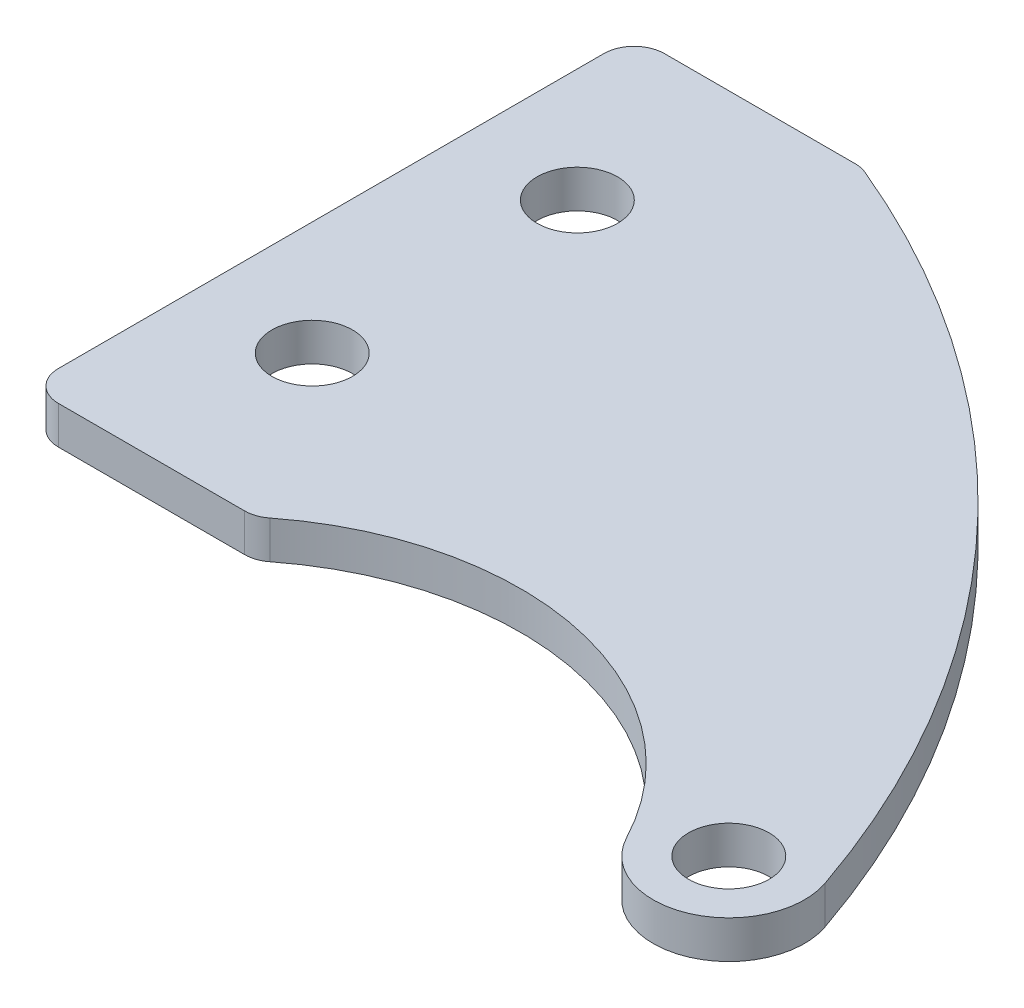
SolidWorks part; units mm, degrees
material "6061-T6 (SS)"
ref_plane "Front" through (0, 0, 0) normal (0, 0, 1) x (1, 0, 0)
ref_plane "Top" through (0, 0, 0) normal (0, 1, 0) x (1, 0, 0)
ref_plane "Right" through (0, 0, 0) normal (1, 0, 0) x (0, 0, -1)
sketch "Sketch1" plane through (0, 0, 0) normal (0, 1, 0) x (1, 0, 0)
  line L1 (0, 50.8) -> (19.05, 50.8)
  line L4 (0, 50.8) -> (0, 0)
  line L6 (0, 0) -> (19.05, 0)
  arc A0 (69.5081, -2.7071) -> (57.8724, -7.704) centre (63.5, -4.7625) cw
  arc A3 (19.05, 0) -> (57.8724, -7.704) centre (35.3619, -19.47) cw
  arc A6 (69.5081, -2.7071) -> (19.05, 50.8) centre (-14.6058, -31.483) ccw
  point P7 (69.251, -2.0703)
  dimension "D1" = 19.05
  dimension "D2" = 4.7625
  dimension "D3" = 6.35
  dimension "D4" = 63.5
  dimension "D6" = 88.9
  dimension "D7" = 25.4
  dimension "D5" = 50.8
extrude "Boss-Extrude1" add sketch "Sketch1" along normal blind 3.175
hole_wizard "1/4 Clearance Hole2" positions "Sketch4" profile "Sketch3" hole size "1/4" standard "ANSI Inch" end condition through all
sketch "Sketch4" plane through (0, 0, 0) normal (0, -1, 0) x (-1, 0, 0)
  point P0 (-63.5, -4.7625)
sketch "Sketch3" plane through (63.5, 0, 4.7625) normal (1, 0, 0) x (0, 0, -1)
  line L0 (0, 0) -> (0, 3.175)
  line L1 (0, 3.175) -> (3.3782, 3.175)
  line L2 (3.3782, 3.175) -> (3.3782, 0)
  line L5 (3.3782, 0) -> (0, 0)
  line L11 (0, -6.35) -> (0, 107.95) construction
  dimension "Thru Hole Dia." = 6.7564
  dimension "Thru Hole Depth" = 3.175
hole_wizard "1/4 Clearance Hole1" positions "Sketch7" profile "Sketch8" hole size "1/4" standard "ANSI Inch" end condition through all
sketch "Sketch7" plane through (0, 3.175, 0) normal (0, 1, 0) x (1, 0, 0)
  line L9 (9.525, 0) -> (9.525, 14.2875) construction
  line L10 (0, 0) -> (19.05, 0) construction
  line L11 (9.525, 14.2875) -> (9.525, 36.5125) construction
  line L12 (9.525, 36.5125) -> (9.525, 50.8) construction
  line L13 (19.05, 50.8) -> (0, 50.8) construction
  point P0 (9.525, 36.5125)
  point P2 (9.525, 14.2875)
  dimension "D1" = 22.225
sketch "Sketch8" plane through (9.525, 3.175, -36.5125) normal (1, 0, 0) x (0, 0, 1)
  line L0 (0, 0) -> (0, 3.175)
  line L1 (0, 3.175) -> (3.3782, 3.175)
  line L2 (3.3782, 3.175) -> (3.3782, 0)
  line L5 (3.3782, 0) -> (0, 0)
  line L11 (0, -6.35) -> (0, 107.95) construction
  dimension "Thru Hole Dia." = 6.7564
  dimension "Thru Hole Depth" = 3.175
fillet "Fillet1" radius 2.54 4 edges at (19.05, 1.5875, 0) (0, 1.5875, 0) (0, 1.5875, -50.8) (19.05, 1.5875, -50.8)
